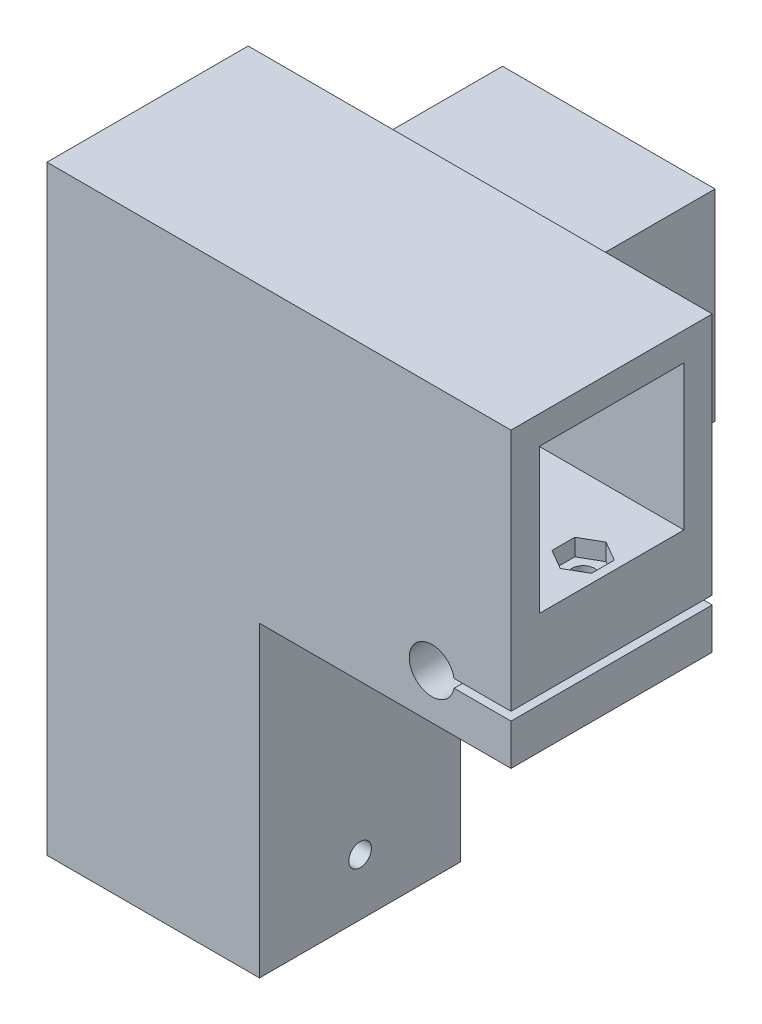
SolidWorks part; units mm, degrees
ref_plane "Front Plane" through (0, 0, 0) normal (0, 0, 1) x (1, 0, 0)
ref_plane "Top Plane" through (0, 0, 0) normal (0, 1, 0) x (1, 0, 0)
ref_plane "Right Plane" through (0, 0, 0) normal (1, 0, 0) x (0, 0, -1)
sketch "Sketch1" plane through (0, 0, 0) normal (1, 0, 0) x (0, 0, -1)
  line L0 (0, 0) -> (85.6, 0)
  line L1 (85.6, 0) -> (85.6, -35.6)
  line L2 (85.6, -35.6) -> (35.6, -35.6)
  line L3 (35.6, -35.6) -> (35.6, -85.6)
  line L4 (35.6, -85.6) -> (0, -85.6)
  line L5 (0, -85.6) -> (0, 0)
  line L6 (5, -5) -> (80.6, -5)
  line L7 (80.6, -5) -> (80.6, -30.6)
  line L8 (80.6, -30.6) -> (30.6, -30.6)
  line L9 (30.6, -30.6) -> (30.6, -80.6)
  line L10 (30.6, -80.6) -> (5, -80.6)
  line L11 (5, -80.6) -> (5, -5)
  line L12 (30.6, -30.6) -> (30.6, -5)
  line L13 (30.6, -30.6) -> (5, -30.6)
  dimension "D1" = 35.6
  dimension "D2" = 35.6
  dimension "D3" = 50
  dimension "D4" = 5
extrude "Boss-Extrude1" add sketch "Sketch1" along normal blind 35.6 contours L0 L1 L2 L3 L4 L5
shell "Shell1" thickness 5 removed face at (17.8, -85.6, -17.8) removed face at (17.8, -17.8, -85.6)
sketch "Sketch5" plane through (0, 0, 0) normal (0, 1, 0) x (1, 0, 0)
  line L4 (0, 35.6) -> (0, 0)
  line L5 (35.6, 35.6) -> (0, 35.6)
  line L6 (35.6, 0) -> (35.6, 35.6)
  line L7 (0, 0) -> (35.6, 0)
  line L8 (0, 35.6) -> (0, 0)
  line L9 (35.6, 35.6) -> (0, 35.6)
  line L10 (35.6, 0) -> (35.6, 35.6)
  line L11 (0, 0) -> (35.6, 0)
  dimension "D1" = 0
extrude "Cut-Extrude2" cut sketch "Sketch5" against normal blind 5
sketch "Sketch6" plane through (0, 0, 0) normal (-1, 0, 0) x (0, 0, 1)
  line L0 (-5, 0) -> (-5, 20.6)
  line L1 (-35.6, -5) -> (-30.6, -5)
  line L2 (-35.6, -5) -> (-35.6, 25.6)
  line L3 (-35.6, 25.6) -> (0, 25.6)
  line L4 (0, -5) -> (0, 25.6)
  line L5 (-30.6, 20.6) -> (-5, 20.6)
  line L6 (-30.6, 0) -> (-30.6, 20.6)
  line L8 (-5, 0) -> (-5, -5)
  line L9 (-30.6, 0) -> (-30.6, -5)
  line L10 (-5, -5) -> (0, -5)
  line L11 (-35.6, -5) -> (0, -5) construction
  line L12 (-30.6, 0) -> (-5, 0) construction
  line M10 (0, -5) -> (-35.6, -5)
  dimension "D1" = 30.6
  dimension "D2" = 35.6
  dimension "D3" = 5
extrude "Boss-Extrude2" add sketch "Sketch6" against normal blind 85
extrude "Boss-Extrude3" add sketch "Sketch6<2>" against normal blind 5 contours L6 L9 L8 L0 L5 M10 region at (0, 7.8, -17.8)
sketch "Sketch6<2>" plane through (0, 0, 0) normal (-1, 0, 0) x (0, 0, 1) same geometry as "Sketch6"
sketch "Sketch7" plane through (85, 0, 0) normal (1, 0, 0) x (0, 0, -1)
  line L0 (0, -5) -> (0, -10)
  line L1 (0, -10) -> (35.6, -10)
  line L2 (35.6, -10) -> (35.6, -5)
  line L3 (5, -5) -> (30.6, -5) construction
  line L4 (5, -5) -> (30.6, -5)
  line L5 (35.6, -5) -> (30.6, -5) construction
  line L6 (5, -5) -> (0, -5) construction
  line L7 (35.6, -5) -> (30.6, -5)
  line L8 (5, -5) -> (0, -5)
  dimension "D1" = 5
extrude "Boss-Extrude4" add sketch "Sketch7" against normal up to surface (49.4 mm away) up to face at (35.6, -26.24, -34.92)
sketch "Sketch8" plane through (0, 0, 0) normal (0, 0, 1) x (1, 0, 0)
  line L0 (68.1, -5) -> (68.1, -18.241) construction
  line L1 (68.1, -18.241) -> (30.6, -18.241) construction
  line L2 (68.1, -18.241) -> (82.1, -18.241) construction
  line L3 (72.0291, -17.491) -> (82.1, -17.491)
  line L4 (68.1, -17.491) -> (82.1, -17.491) construction
  line L5 (72.0291, -18.991) -> (82.1, -18.991)
  line L6 (5, 20.6) -> (5, -85.6)
  line L7 (85, 20.6) -> (5, 20.6)
  line L8 (85, 20.6) -> (5, 20.6)
  line L10 (30.6, -85.6) -> (30.6, -5)
  line L11 (5, -85.6) -> (30.6, -85.6)
  line L12 (5, 20.6) -> (5, -85.6)
  line L16 (30.6, -85.6) -> (30.6, -5) construction
  line L17 (5, -85.6) -> (30.6, -85.6)
  line L18 (68.1, -18.991) -> (82.1, -18.991) construction
  line L19 (68.1, -26.241) -> (30.6, -26.241) construction
  line L21 (68.1, -26.241) -> (82.1, -26.241)
  line L22 (68.1, -26.241) -> (35.6, -26.241)
  line L23 (82.1, -18.991) -> (82.1, -26.241)
  line L24 (82.1, -17.491) -> (82.1, -10)
  line L25 (35.6, -10) -> (85, -10) construction
  line L26 (35.6, -85.6) -> (35.6, -10) construction
  line L27 (35.6, -26.241) -> (35.6, -10)
  line L28 (35.6, -10) -> (85, -10)
  line L30 (68.1, -18.991) -> (30.6, -18.991) construction
  line L32 (68.1, -17.491) -> (30.6, -17.491) construction
  line L35 (68.1, -26.241) -> (68.1, 2.4755) construction
  line L36 (85, -5) -> (85, 20.6)
  line L37 (85, -5) -> (85, 20.6)
  line L38 (30.6, -5) -> (85, -5)
  line L39 (30.6, -5) -> (85, -5)
  arc A0 (72.0291, -17.491) -> (72.0291, -18.991) centre (68.1, -18.241) ccw
  line M11 (35.6, -85.6) -> (35.6, -10)
  line M12 (35.6, -10) -> (85, -10)
  dimension "D4" = 8
  dimension "D2" = 37.5
  dimension "D3" = 13.241
  dimension "D5" = 14
  dimension "D1" = 0
  dimension "D6" = 0.75
  dimension "D7" = 0.75
  dimension "D9" = 8
extrude "Boss-Extrude5" add sketch "Sketch8" against normal up to surface (35.6 mm away) contours A0 L3 L24 L22 L21 L23 L5 M12 M11 region at (57.7786, -18.1091, 0) up to face at (40.2, 5.2, -35.6)
sketch "Sketch10" plane through (85, 0, 0) normal (1, 0, 0) x (0, 0, -1)
  line L4 (35.6, -10) -> (35.6, 25.6)
  line L5 (35.6, 25.6) -> (0, 25.6)
  line L6 (0, 25.6) -> (0, -10)
  line L7 (0, -10) -> (35.6, -10)
  line L8 (35.6, -10) -> (35.6, 25.6)
  line L9 (35.6, 25.6) -> (0, 25.6)
  line L10 (0, 25.6) -> (0, -10)
  line L11 (0, -10) -> (35.6, -10)
  dimension "D1" = 0
extrude "Cut-Extrude3" cut sketch "Sketch10" against normal up to surface (2.9 mm away) up to face at (82.1, -13.7455, -17.8)
sketch "Sketch13" plane through (0, -85.6, 0) normal (0, -1, 0) x (1, 0, 0)
  line L4 (0, 0) -> (0, -35.6)
  line L5 (0, -35.6) -> (35.6, -35.6)
  line L6 (35.6, -35.6) -> (35.6, 0)
  line L7 (35.6, 0) -> (0, 0)
  line L8 (0, 0) -> (0, -35.6)
  line L9 (0, -35.6) -> (35.6, -35.6)
  line L10 (35.6, -35.6) -> (35.6, 0)
  line L11 (35.6, 0) -> (0, 0)
  line M5 (0, 0) -> (0, -35.6)
  line M6 (0, -35.6) -> (35.6, -35.6)
  line M7 (35.6, -35.6) -> (35.6, 0)
  line M8 (35.6, 0) -> (0, 0)
  line M9 (30.6, -30.6) -> (5, -30.6)
  line M10 (5, -30.6) -> (5, -5)
  line M11 (5, -5) -> (30.6, -5)
  line M12 (30.6, -5) -> (30.6, -30.6)
  dimension "D1" = 0
extrude "Cut-Extrude4" cut sketch "Sketch13" against normal blind 5 contours M9 M12 M11 M10 | M8 M5 M6 M7 M12 M9 M10 M11 region at (17.8, -85.6, -0.5035) region at (17.8, -85.6, -17.8)
sketch "Sketch14" plane through (0, 0, -85.6) normal (0, 0, -1) x (-1, 0, 0)
  line L4 (0, -35.6) -> (0, 0)
  line L5 (0, 0) -> (-35.6, 0)
  line L6 (-35.6, 0) -> (-35.6, -35.6)
  line L7 (-35.6, -35.6) -> (0, -35.6)
  line L8 (0, -35.6) -> (0, 0)
  line L9 (0, 0) -> (-35.6, 0)
  line L10 (-35.6, 0) -> (-35.6, -35.6)
  line L11 (-35.6, -35.6) -> (0, -35.6)
  dimension "D1" = 0
extrude "Cut-Extrude5" cut sketch "Sketch14" against normal blind 5
sketch "Sketch15" plane through (0, -5, 0) normal (0, 1, 0) x (1, 0, 0)
  line L0 (82.1, 17.8) -> (72.0291, 17.8)
  line L1 (82.1, 5) -> (82.1, 30.6) construction
  line L2 (72.0291, 35.6) -> (72.0291, 0) construction
  line L3 (35.6, 17.8) -> (47.6, 17.8) construction
  line L4 (77.0645, 13.7585) -> (80.5645, 15.7793)
  line L5 (80.5645, 15.7793) -> (80.5645, 19.8207)
  line L6 (80.5645, 19.8207) -> (77.0645, 21.8415)
  line L7 (77.0645, 21.8415) -> (73.5645, 19.8207)
  line L8 (73.5645, 19.8207) -> (73.5645, 15.7793)
  line L9 (73.5645, 15.7793) -> (77.0645, 13.7585)
  line L10 (35.6, 35.6) -> (35.6, 0) construction
  line L12 (47.6, 13.7585) -> (51.1, 15.7793)
  line L13 (51.1, 15.7793) -> (51.1, 19.8207)
  line L14 (51.1, 19.8207) -> (47.6, 21.8415)
  line L15 (47.6, 21.8415) -> (44.1, 19.8207)
  line L16 (44.1, 19.8207) -> (44.1, 15.7793)
  line L17 (44.1, 15.7793) -> (47.6, 13.7585)
  circle A0 centre (77.0645, 17.8) radius 2
  circle A1 centre (77.0645, 17.8) radius 3.5 construction
  circle A2 centre (47.6, 17.8) radius 2
  circle A3 centre (47.6, 17.8) radius 3.5 construction
  dimension "D2" = 4
  dimension "D5" = 4
  dimension "D1" = 7
  dimension "D3" = 12
  dimension "D4" = 7
extrude "Cut-Extrude7" cut sketch "Sketch15" against normal blind 3 contours A0 L0 L5 L6 L7 L8 | A0 L0 L8 L9 L4 L5 | L16 L17 L12 L13 L14 L15 A2 region at (80.4837, -5, -16.7896) region at (79.8145, -5, -17.8808) region at (45.9035, -5, -14.8615)
sketch "Sketch16" plane through (35.6, 0, 0) normal (1, 0, 0) x (0, 0, -1)
  line L0 (80.6, -17.8) -> (70.6, -17.8) construction
  line L1 (80.6, 0) -> (80.6, -35.6) construction
  line L2 (35.6, -17.8) -> (45.6, -17.8) construction
  line L3 (35.6, -26.241) -> (35.6, 0) construction
  line L4 (17.8, -26.241) -> (17.8, -36.241) construction
  line L5 (35.6, -26.241) -> (0, -26.241) construction
  line L6 (17.8, -80.6) -> (17.8, -70.6) construction
  line L7 (35.6, -80.6) -> (0, -80.6) construction
  line L9 (21.8415, -36.241) -> (19.8207, -32.741)
  line L10 (19.8207, -32.741) -> (15.7793, -32.741)
  line L11 (15.7793, -32.741) -> (13.7585, -36.241)
  line L12 (13.7585, -36.241) -> (15.7793, -39.741)
  line L13 (15.7793, -39.741) -> (19.8207, -39.741)
  line L14 (19.8207, -39.741) -> (21.8415, -36.241)
  line L15 (21.8414, -70.5876) -> (19.81, -67.0938)
  line L16 (19.81, -67.0938) -> (15.7685, -67.1062)
  line L17 (15.7685, -67.1062) -> (13.7586, -70.6124)
  line L18 (13.7586, -70.6124) -> (15.79, -74.1062)
  line L19 (15.79, -74.1062) -> (19.8315, -74.0938)
  line L20 (19.8315, -74.0938) -> (21.8414, -70.5876)
  line L21 (70.47, -21.8394) -> (74.0332, -19.9322)
  line L22 (74.0332, -19.9322) -> (74.1632, -15.8929)
  line L23 (74.1632, -15.8929) -> (70.73, -13.7606)
  line L24 (70.73, -13.7606) -> (67.1668, -15.6678)
  line L25 (67.1668, -15.6678) -> (67.0368, -19.7071)
  line L26 (67.0368, -19.7071) -> (70.47, -21.8394)
  line L27 (45.6069, -21.8414) -> (49.1035, -19.8147)
  line L28 (49.1035, -19.8147) -> (49.0965, -15.7733)
  line L29 (49.0965, -15.7733) -> (45.5931, -13.7586)
  line L30 (45.5931, -13.7586) -> (42.0965, -15.7853)
  line L31 (42.0965, -15.7853) -> (42.1035, -19.8267)
  line L32 (42.1035, -19.8267) -> (45.6069, -21.8414)
  circle A0 centre (45.6, -17.8) radius 2
  circle A1 centre (70.6, -17.8) radius 2
  circle A2 centre (17.8, -36.241) radius 2
  circle A3 centre (17.8, -70.6) radius 2
  circle A4 centre (17.8, -36.241) radius 3.5 construction
  circle A5 centre (17.8, -70.6) radius 3.5 construction
  circle A6 centre (70.6, -17.8) radius 3.5 construction
  circle A7 centre (45.6, -17.8) radius 3.5 construction
  circle A8 centre (70.6, -17.8) radius 7.5
  circle A9 centre (45.6, -17.8) radius 7.5
  circle A10 centre (17.8, -36.241) radius 7.5
  circle A11 centre (17.8, -70.6) radius 7.5
  dimension "D2" = 4
  dimension "D4" = 15
  dimension "D1" = 10
  dimension "D3" = 7
extrude "Cut-Extrude8" cut sketch "Sketch16" against normal blind 10 contours A0 | A2 | A1 | A3 region at (35.6, -17.8, -45.6) region at (35.6, -36.241, -17.8)
extrude "Cut-Extrude9" cut sketch "Sketch16<3>" against normal blind 3 from offset 2 contours L13 L14 L9 L10 L11 L12 A2 | L31 L32 L27 L28 L29 L30 A0 | L25 L26 L21 L22 L23 L24 A1 | L15 L16 L17 L18 L19 L20 region at (35.6, -37.9375, -20.7385) region at (35.6, -20.6817, -68.8103) region at (35.6, -20.7414, -43.9085) offset against normal yes
sketch "Sketch16<3>" plane through (35.6, 0, 0) normal (1, 0, 0) x (0, 0, -1) same geometry as "Sketch16"
sketch "Sketch18" plane through (35.6, 0, 0) normal (1, 0, 0) x (0, 0, -1)
  line L8 (80.6, -35.6) -> (80.6, 0)
  line L9 (80.6, 0) -> (35.6, 0)
  line L10 (35.6, 0) -> (35.6, -26.241)
  line L11 (35.6, -26.241) -> (0, -26.241)
  line L12 (0, -26.241) -> (0, -80.6)
  line L13 (0, -80.6) -> (35.6, -80.6)
  line L14 (35.6, -80.6) -> (35.6, -35.6)
  line L15 (35.6, -35.6) -> (80.6, -35.6)
  line L16 (80.6, -35.6) -> (80.6, 0)
  line L17 (80.6, 0) -> (35.6, 0)
  line L18 (35.6, 0) -> (35.6, -26.241)
  line L19 (35.6, -26.241) -> (0, -26.241)
  line L20 (0, -26.241) -> (0, -80.6)
  line L21 (0, -80.6) -> (35.6, -80.6)
  line L22 (35.6, -80.6) -> (35.6, -35.6)
  line L23 (35.6, -35.6) -> (80.6, -35.6)
  circle M9 centre (17.8, -70.6) radius 2
  circle M10 centre (70.6, -17.8) radius 2
  circle M11 centre (17.8, -36.241) radius 2
  circle M12 centre (45.6, -17.8) radius 2
  line M13 (80.6, -35.6) -> (80.6, 0)
  line M14 (80.6, 0) -> (35.6, 0)
  line M15 (35.6, 0) -> (35.6, -26.241)
  line M16 (35.6, -26.241) -> (0, -26.241)
  line M17 (0, -26.241) -> (0, -80.6)
  line M18 (0, -80.6) -> (35.6, -80.6)
  line M19 (35.6, -80.6) -> (35.6, -35.6)
  line M20 (35.6, -35.6) -> (80.6, -35.6)
  dimension "D1" = 0
extrude "Boss-Extrude7" add sketch "Sketch18" along normal blind 2 contours M20 M13 M14 M15 M16 M17 M18 M19 M10 M12 M11 M9 region at (35.6, -34.4601, -58.1)
sketch "Sketch20" plane through (0, -5, 0) normal (0, 1, 0) x (1, 0, 0)
  circle A0 centre (77.0645, 17.8) radius 2 construction
  circle A1 centre (47.6, 17.8) radius 2 construction
  circle A2 centre (77.0645, 17.8) radius 2
  circle A3 centre (47.6, 17.8) radius 2
extrude "Cut-Extrude10" cut sketch "Sketch20" against normal blind 24
